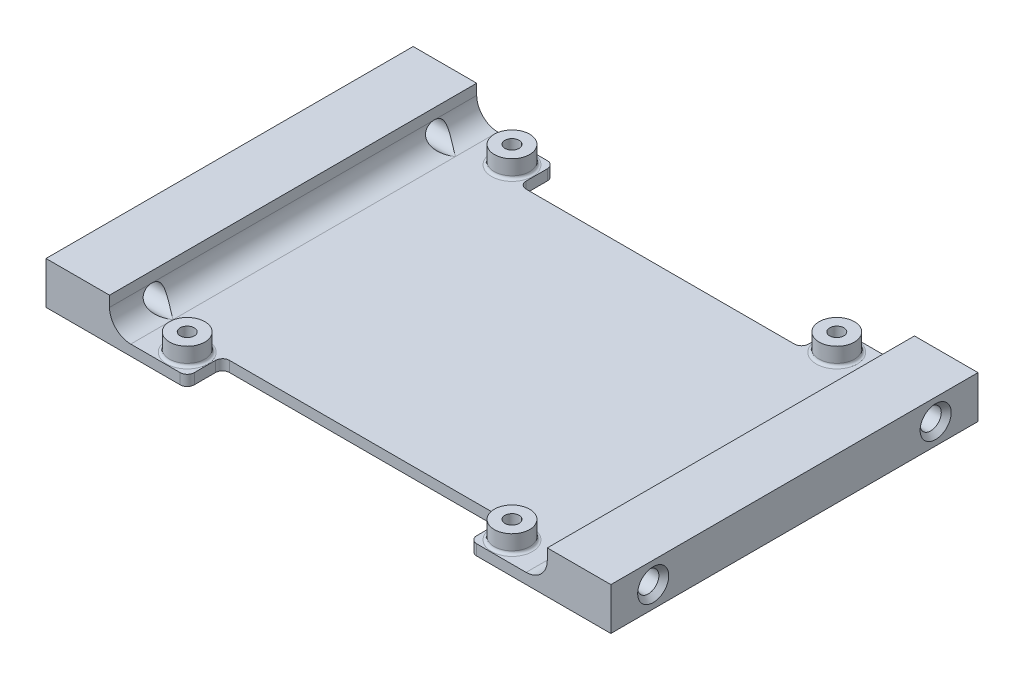
SolidWorks part; units mm, degrees
material "ABS"
ref_plane "Ebene vorne" through (0, 0, 0) normal (0, 0, 1) x (1, 0, 0)
ref_plane "Ebene oben" through (0, 0, 0) normal (0, 1, 0) x (1, 0, 0)
ref_plane "Ebene rechts" through (0, 0, 0) normal (1, 0, 0) x (0, 0, -1)
sketch "Skizze1" plane through (0, 0, 0) normal (0, 1, 0) x (1, 0, 0)
  line L0 (0, 54.393) -> (0, -53.8733) construction
  line L1 (-66.3304, 0) -> (64.6286, 0) construction
  line L2 (-40, -26) -> (-40, 26)
  line L3 (-40, 26) -> (40, 26)
  line L4 (40, -26) -> (40, 26)
  line L5 (-40, -26) -> (40, -26)
  point P9 (0, 26)
  point P10 (0, -26)
  point P12 (40, 0)
  point P13 (-40, 0)
  dimension "D1" = 80
  dimension "D2" = 52
extrude "Aufsatz-Linear austragen1" add sketch "Skizze1" along normal blind 3 and the other way blind 3
hole_wizard "Ø3.0 (3) Durchmesser Bohrung1" positions "Skizze3" profile "Skizze2" hole size "Ø3.0" standard "ANSI Metrisch"
sketch "Skizze3" plane through (40, 0, 0) normal (1, 0, 0) x (0, 0, -1)
  line L0 (-52.199, 0) -> (56.2959, 0) construction
  line L3 (0, 17.1411) -> (0, -14.5971) construction
  point P0 (-20, 0)
  point P17 (20, 0)
  dimension "D1" = 40
sketch "Skizze2" plane through (40, 0, 20) normal (0, 1, 0) x (0, 0, -1)
  line L0 (0, 0) -> (0, 10.9013)
  line L1 (0, 10.9013) -> (1.5, 10)
  line L2 (1.5, 10) -> (1.5, 0)
  line L5 (1.5, 0) -> (0, 0)
  line L10 (0, 10.9013) -> (-1.5, 10) construction
  line L11 (0, -6.35) -> (0, 107.95) construction
  dimension "Bohrerdurchmesser" = 3
  dimension "Bohrungstiefe" = 10
  dimension "Spitzenwinkel" = 118
mirror "Spiegeln1" about plane through (0, 0, 0) normal (1, 0, 0) of "Ø3.0 (3) Durchmesser Bohrung1"
sketch "Skizze4" plane through (0, 3, 0) normal (0, 1, 0) x (1, 0, 0)
  line L0 (0, 34.94) -> (0, -42.5549) construction
  line L1 (-31, 26) -> (31, 26)
  line L2 (-31, 26) -> (-31, -26)
  line L3 (-31, -26) -> (31, -26)
  line L4 (31, 26) -> (31, -26)
  line L5 (-49.9218, 0) -> (29.7382, 0) construction
  line L6 (-40, -26) -> (40, -26) construction
  point P11 (31, 26)
  point P14 (-31, 26)
  point P17 (-31, -29)
  dimension "D1" = 55
  dimension "D2" = 62
extrude "Schnitt-Linear austragen1" cut sketch "Skizze4" against normal offset from surface (4.5 mm away) 1.5 up to face at (0, -3, 0)
sketch "Skizze10" plane through (0, -1.5, 0) normal (0, 1, 0) x (1, 0, 0)
  line L0 (0, 42.5002) -> (0, -29.2377) construction
  line L1 (-53.6527, 0) -> (59.7816, 0) construction
  line L2 (-31, 15) -> (31, 15)
  line L4 (31, -26) -> (31, 26) construction
  line L5 (31, 15) -> (31, 18)
  line L6 (31, 20) -> (31, -20) construction
  line L7 (31, 18) -> (-31, 18)
  line L8 (-31, 15) -> (-31, 18)
  line L9 (-31, -15) -> (-31, -18)
  line L10 (31, -18) -> (-31, -18)
  line L11 (31, -15) -> (31, -18)
  line L12 (-31, -15) -> (31, -15)
  line L13 (-50.3653, 16.5) -> (54.8764, 16.5) construction
  line L14 (-45.6119, -16.5) -> (54.8764, -16.5) construction
  point P7 (0, 18)
  point P15 (0, 15)
  point P16 (0, -15)
  point P17 (0, -18)
  dimension "D1" = 3
  dimension "D2" = 33
extrude "Aufsatz-Linear austragen3" [suppressed] add sketch "Skizze10" along normal blind 2
sketch "Skizze8" plane through (0, -1.5, 0) normal (0, 1, 0) x (1, 0, 0)
  line L0 (0, 55.3802) -> (0, -47.9549) construction
  line L1 (-52.26, 0) -> (58.0495, 0) construction
  circle A0 centre (-23, 23) radius 2.5
  circle A1 centre (23, 23) radius 2.5
  circle A2 centre (23, -23) radius 2.5
  circle A3 centre (-23, -23) radius 2.5
  dimension "D1" = 5
  dimension "D2" = 46
  dimension "D3" = 46
extrude "Aufsatz-Linear austragen2" add sketch "Skizze8" along normal blind 2.5
sketch "Skizze9" plane through (0, 1, 0) normal (0, 1, 0) x (1, 0, 0)
  circle A0 centre (-23, 23) radius 1
  circle A1 centre (23, 23) radius 1
  circle A2 centre (23, -23) radius 1
  circle A3 centre (-23, -23) radius 1
  dimension "D1" = 2
extrude "Schnitt-Linear austragen5" cut sketch "Skizze9" against normal through all
sketch "Skizze11" plane through (0, 0, 0) normal (0, 1, 0) x (1, 0, 0)
  line L0 (-53.2341, 0) -> (61.4059, 0) construction
  line L1 (0, 40.407) -> (0, -28.2162) construction
  line L2 (-20, 26) -> (-20, 21)
  line L3 (-31, 26) -> (31, 26) construction
  line L4 (-20, 21) -> (20, 21)
  line L5 (-20, 26) -> (20, 26)
  line L6 (20, 26) -> (20, 21)
  line L7 (20, -26) -> (20, -21)
  line L8 (-20, -26) -> (20, -26)
  line L9 (-20, -21) -> (20, -21)
  line L10 (-20, -26) -> (-20, -21)
  point P10 (0, -21)
  point P12 (0, 26)
  point P13 (0, 21)
  point P14 (0, -26)
  dimension "D1" = 5
  dimension "D3" = 40
extrude "Schnitt-Linear austragen6" cut sketch "Skizze11" against normal through all
fillet "Verrundung2" radius 0.4 4 edges at (23, -1.5, 25.5) (-23, -1.5, 20.5) (23, -1.5, -25.5) (-23, -1.5, -20.5)
chamfer "Fase1" distance 0.7 angle 45 4 edges at (-40, 0, -18.5) (-40, 0, 21.5) (40, 0, 18.5) (40, 0, -21.5)
fillet "Verrundung4" radius 1 8 edges at (-20, -2.25, -26) (-20, -2.25, -21) (20, -2.25, -26) (20, -2.25, -21) (20, -2.25, 26) (20, -2.25, 21) (-20, -2.25, 21) (-20, -2.25, 26)
fillet "Verrundung5" radius 3 6 edges at (-31, -1.5, 23) (-31, -1.5, -23) (31, -1.5, -23) (31, -1.5, 23) (-31, -1.5, 0) (31, -1.5, 0)
ref_axis "Achse1" through (-44, 0, 0) along (1, 0, 0)
ref_axis "Achse2" through (0, 0, -37.4) along (0, 0, 1)
ref_axis "Achse3" through (0, -3.3455, 0) along (0, 1, 0)
